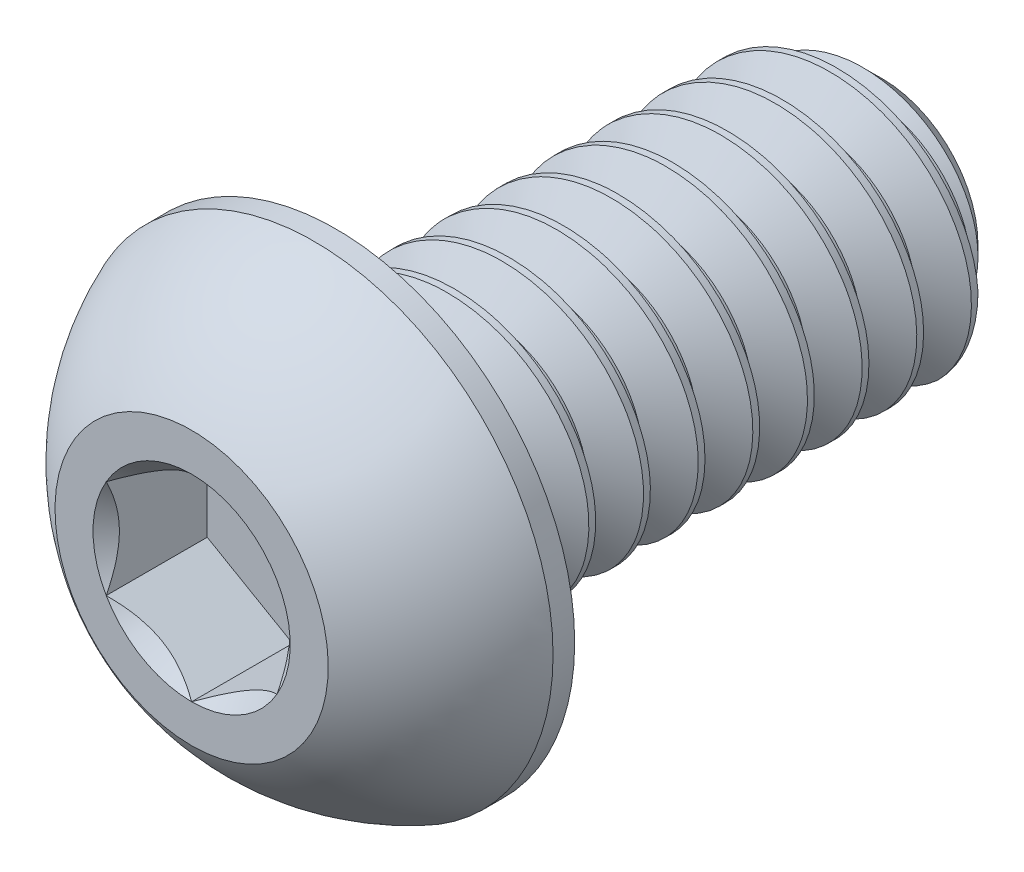
SolidWorks part; units mm, degrees
ref_plane "Front" through (0, 0, 0) normal (0, 0, 1) x (1, 0, 0)
ref_plane "Top" through (0, 0, 0) normal (0, 1, 0) x (1, 0, 0)
ref_plane "Right" through (0, 0, 0) normal (1, 0, 0) x (0, 0, -1)
sketch "Sketch1" plane through (0, 0, 0) normal (1, 0, 0) x (0, 0, -1)
  line L2 (3.3528, 3.175) -> (16.0528, 3.175)
  line L3 (16.0528, 3.175) -> (16.0528, 0)
  line L4 (16.0528, 0) -> (3.3528, 0)
  line L6 (2.8499, 5.5499) -> (3.3528, 5.5499) construction
  line L7 (16.0528, 3.175) -> (16.0528, -3.175) construction
  line L8 (0, 0) -> (3.3528, 0) construction
  line L9 (3.3528, 5.5499) -> (3.3528, -5.5499) construction
  line L11 (3.3528, 3.175) -> (3.3528, 0)
  line L13 (0, 1.9844) -> (0, -1.9844) construction
  line L14 (0, 1.9844) -> (0, 3.175) construction
  arc A3 (0, 3.175) -> (2.8499, 5.5499) centre (5.0603, 0) cw construction
  dimension "D1" = 0.5029
  dimension "Head Ht" = 3.3528
  dimension "Head Dia" = 11.0998
  dimension "Dia" = 6.35
  dimension "Lg" = 12.7
  dimension "Hex" = 3.9688
revolve "Revolve1" add sketch "Sketch1" angle 360 mid plane about L4
sketch "Sketch3" plane through (0, 0, -16.0528) normal (0, 0, -1) x (-1, 0, 0)
  circle A0 centre (0, 0) radius 3.175
curve "Helix/Spiral1" pitch 1.27 height 13.97 radius 3.175 centre (0, 0, -16.0528) axis (0, 0, 1) start towards (0, 1, 0)
sketch "Sketch2" plane through (0, 0, 0) normal (1, 0, 0) x (0, 0, -1)
  line L0 (16.0528, 3.175) -> (17.164, 3.175)
  line L1 (17.164, 3.175) -> (16.6878, 2.3501)
  line L2 (16.6878, 2.3501) -> (16.529, 2.3501)
  line L3 (16.529, 2.3501) -> (16.0528, 3.175)
  line L4 (16.2909, 2.7626) -> (16.9259, 2.7626) construction
  dimension "D1" = 60
  dimension "D2" = 0.1588
  dimension "D3" = 0.635
chamfer "Chamfer1" distance 0.9525 angle 45 1 edges at (0, 3.175, -16.0528)
sweep "Cut-Sweep1" cut profiles "Sketch2" path "Helix/Spiral1" align with end faces yes
sketch "Sketch7" plane through (0, 0, 0) normal (1, 0, 0) x (0, 0, -1)
  line L6 (2.8499, 5.5499) -> (3.3528, 5.5499) construction
  line L8 (0, 0) -> (3.3528, 0) construction
  line L11 (3.3528, 5.5499) -> (3.3528, -5.5499) construction
  line L12 (2.8499, 5.5499) -> (3.3528, 5.5499)
  line L13 (0, 0) -> (3.3528, 0)
  line L14 (0, 1.9844) -> (0, -1.9844) construction
  line L15 (3.3528, 5.5499) -> (3.3528, 0)
  line L16 (0, 3.175) -> (0, 0)
  arc A2 (2.8499, 5.5499) -> (0, 3.175) centre (5.0603, 0) ccw construction
  arc A3 (2.8499, 5.5499) -> (0, 3.175) centre (5.0603, 0) ccw
revolve "Revolve2" add sketch "Sketch7" angle 360 mid plane about L13
sketch "Sketch5" plane through (0, 0, 0) normal (0, 0, 1) x (1, 0, 0)
  line L1 (1.9844, -1.1457) -> (1.9844, 1.1457)
  line L2 (1.9844, 1.1457) -> (0, 2.2914)
  line L3 (0, 2.2914) -> (-1.9844, 1.1457)
  line L4 (-1.9844, 1.1457) -> (-1.9844, -1.1457)
  line L5 (-1.9844, -1.1457) -> (0, -2.2914)
  line L6 (0, -2.2914) -> (1.9844, -1.1457)
  circle A0 centre (0, 0) radius 1.9844 construction
extrude "Cut-Extrude2" cut sketch "Sketch5" against normal blind 2.347
sketch "Sketch6" plane through (0, 0, 0) normal (0, 0, 1) x (1, 0, 0)
  circle A0 centre (0, 0) radius 2.2914
extrude "Cut-Extrude3" cut sketch "Sketch6" against normal blind 2.347 draft 45
sketch "Sketch9" [suppressed] plane through (0, 0, -3.3528) normal (0, 0, 1) x (1, 0, 0)
  circle A2 centre (0, 0) radius 3.175
extrude "Boss-Extrude2" [suppressed] add sketch "Sketch9" against normal offset from surface (25.4 mm away) 22.225 up to face at (0, 2.2225, -16.0528)
sketch "Sketch10" plane through (0, 0, 0) normal (1, 0, 0) x (0, 0, -1)
  line L0 (16.0528, 3.175) -> (16.0528, -3.175) construction
  point P0 (14.1478, -3.175)
  dimension "D1" = 1.905
equation "\"D3@Helix/Spiral1\" = \"Lg@Sketch1\" + \"D4@Helix/Spiral1\""
equation "\"D2@Sketch2\" = \"D4@Helix/Spiral1\" * .125"
equation "\"D3@Sketch2\" = \"D4@Helix/Spiral1\" * .5"
equation "\"D1@Chamfer1\" = \"D4@Helix/Spiral1\" * .75"
equation "\"D1@Cut-Extrude2\" = \"Head Ht@Sketch1\" * .7"
equation "\"D1@Sketch1\" = \"Head Ht@Sketch1\" * .15"
equation "\"D1@Sketch10\" = \"D4@Helix/Spiral1\" * 1.5"
equation "\"D1@Cut-Extrude3\" = \"D1@Cut-Extrude2\""
